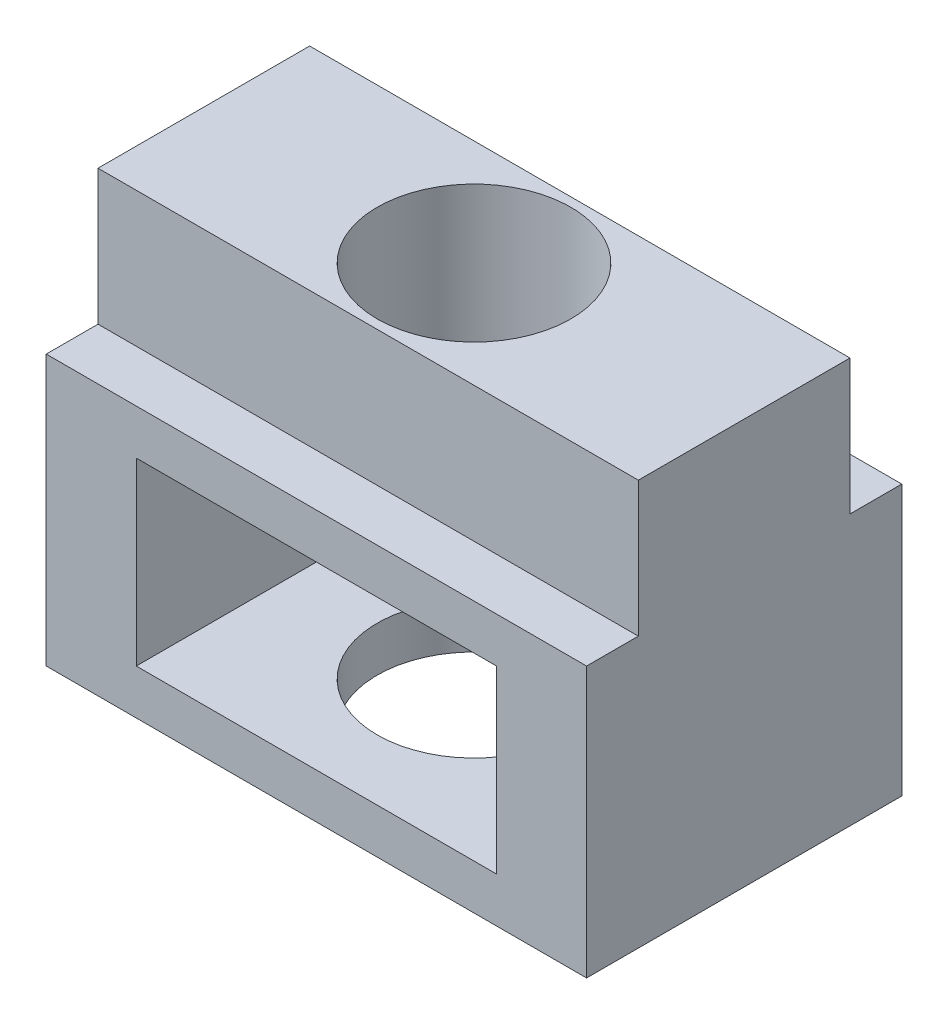
SolidWorks part; units mm, degrees
ref_plane "Plan de face" through (0, 0, 0) normal (0, 0, 1) x (1, 0, 0)
ref_plane "Plan de dessus" through (0, 0, 0) normal (0, 1, 0) x (1, 0, 0)
ref_plane "Plan de droite" through (0, 0, 0) normal (1, 0, 0) x (0, 0, -1)
sketch "Sketch1" plane through (0, 0, 0) normal (0, 1, 0) x (1, 0, 0)
  line L1 (-6, 3.5) -> (6, 3.5)
  line L2 (-6, 3.5) -> (-6, -3.5)
  line L3 (-6, -3.5) -> (6, -3.5)
  line L4 (6, 3.5) -> (6, -3.5)
  line L5 (-6, 3.5) -> (6, -3.5) construction
  line L6 (-6, -3.5) -> (6, 3.5) construction
  point P0 (0, 0)
  dimension "D1" = 7
  dimension "D2" = 12
extrude "Boss-Extrude1" add sketch "Sketch1" along normal blind 6 contours L2 L3 L4 L1
sketch "Sketch2" plane through (0, 6, 0) normal (0, 1, 0) x (1, 0, 0)
  line L0 (6, 3.5) -> (6, -3.5) construction
  line L1 (-6, 2.35) -> (6, 2.35)
  line L2 (-6, 2.35) -> (-6, -2.35)
  line L3 (-6, -2.35) -> (6, -2.35)
  line L4 (6, 2.35) -> (6, -2.35)
  line L5 (-6, 2.35) -> (6, -2.35) construction
  line L6 (-6, -2.35) -> (6, 2.35) construction
  point P0 (0, 0)
  dimension "D1" = 4.7
extrude "Boss-Extrude2" add sketch "Sketch2" along normal blind 3
sketch "Sketch3" plane through (0, 0, 3.5) normal (0, 0, 1) x (1, 0, 0)
  line L0 (0, 0) -> (0, 6) construction
  line L1 (-6, 6) -> (6, 6) construction
  line L3 (-4, 5) -> (4, 5)
  line L4 (-4, 5) -> (-4, 1)
  line L5 (-4, 1) -> (4, 1)
  line L6 (4, 5) -> (4, 1)
  line L7 (-4, 5) -> (4, 1) construction
  line L8 (-4, 1) -> (4, 5) construction
  point P5 (0, 3)
  dimension "D1" = 8
  dimension "D2" = 4
extrude "Cut-Extrude1" cut sketch "Sketch3" against normal through all
sketch "Sketch4" plane through (0, 9, 0) normal (0, 1, 0) x (1, 0, 0)
  circle A0 centre (0, 0) radius 2.15
  dimension "D1" = 4.3
extrude "Cut-Extrude2" cut sketch "Sketch4" against normal through all
